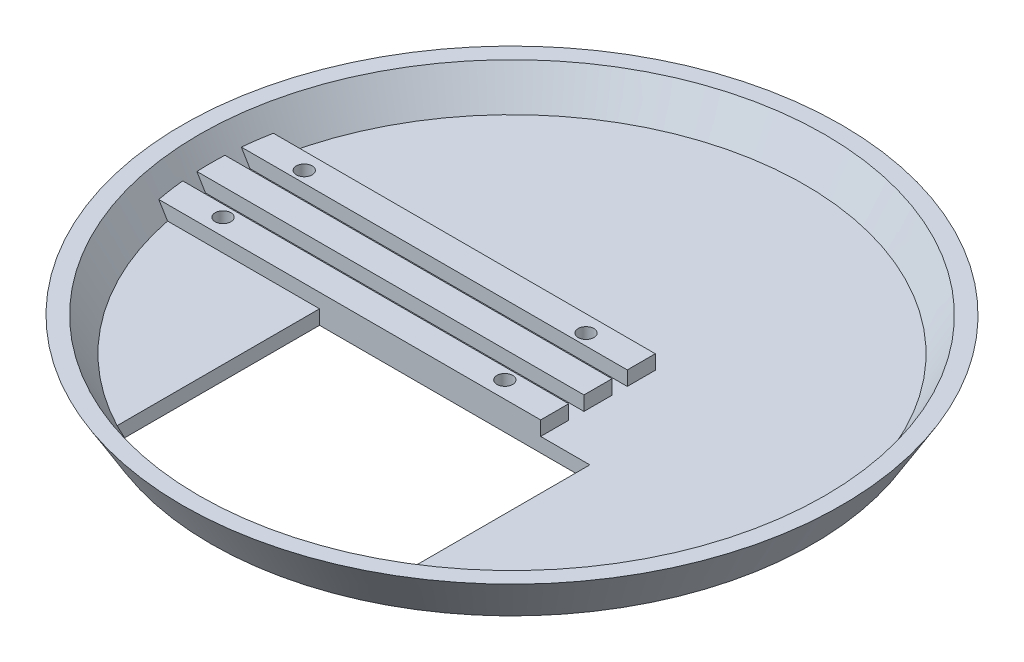
SolidWorks part; units mm, degrees
ref_plane "Front Plane" through (0, 0, 0) normal (0, 0, 1) x (1, 0, 0)
ref_plane "Top Plane" through (0, 0, 0) normal (0, 1, 0) x (1, 0, 0)
ref_plane "Right Plane" through (0, 0, 0) normal (1, 0, 0) x (0, 0, -1)
sketch "Sketch1" plane through (0, 0, 0) normal (0, 0, 1) x (1, 0, 0)
  line L0 (0, 0) -> (63, 0)
  line L1 (63, 0) -> (69, 10)
  line L6 (0, 3) -> (61.3014, 3)
  line L7 (61.3014, 3) -> (65.5014, 10)
  line L8 (69, 10) -> (65.5014, 10)
  line L9 (0, 0) -> (0, 3)
  line L10 (61.3014, 3) -> (66.4275, 11.5435) construction
  dimension "D1" = 69
  dimension "D2" = 63
  dimension "D3" = 10
  dimension "D4" = 3
revolve "Revolve1" add sketch "Sketch1" angle 360 about L9
sketch "Sketch2" plane through (0, 3, 0) normal (0, 1, 0) x (1, 0, 0)
  line L0 (-28.3, -12) -> (-28.3, -54.3781)
  line L1 (-28.3, -12) -> (28.3, -12)
  line L5 (28.3, -12) -> (28.3, -54.3781)
  arc A0 (-28.3, -54.3781) -> (28.3, -54.3781) centre (0, 0) ccw
  circle A3 centre (0, 0) radius 61.3014 construction
  dimension "D2" = 28.3
  dimension "D1" = 56.6
  dimension "D4" = 12
extrude "Cut-Extrude1" cut sketch "Sketch2" against normal through all
sketch "Sketch4" plane through (0, 0, 0) normal (1, 0, 0) x (0, 0, -1)
  line L0 (-6.1333, 3) -> (-12, 3)
  line L5 (-12, 3) -> (-12, 6)
  line L6 (-12, 6) -> (-6.1333, 6)
  line L7 (-6.1333, 6) -> (-6.1333, 3)
  line L8 (-2.9333, 3) -> (2.9333, 3)
  line L9 (2.9333, 3) -> (2.9333, 6)
  line L10 (2.9333, 6) -> (-2.9333, 6)
  line L11 (-2.9333, 6) -> (-2.9333, 3)
  line L12 (12, 3) -> (6.1333, 3)
  line L13 (6.1333, 3) -> (6.1333, 6)
  line L14 (6.1333, 6) -> (12, 6)
  line L15 (12, 6) -> (12, 3)
  point P13 (0, 3)
  dimension "D1" = 12
  dimension "D2" = 3
  dimension "D3" = 3
  dimension "D4" = 3.2
  dimension "D5" = 3.2
  dimension "D6" = 12
extrude "Boss-Extrude1" add sketch "Sketch4" along normal blind 10 and the other way blind 63.5
sketch "Sketch5" plane through (0, 0, 0) normal (0, 1, 0) x (1, 0, 0)
  line L0 (10, 2.9333) -> (10, -2.9333) construction
  circle A0 centre (7, -8.5) radius 1.65
  circle A1 centre (7, 0) radius 1.65
  circle A2 centre (7, 8.5) radius 1.65
  circle A6 centre (-52, 8.5) radius 1.65
  circle A8 centre (-52, -8.5) radius 1.65
  circle A9 centre (-22.5, 0) radius 1.65 [skipped]
  circle A10 centre (-52, 0) radius 1.65 [skipped]
  circle A11 centre (-22.5, 8.5) radius 1.65 [skipped]
  circle A12 centre (-22.5, -8.5) radius 1.65 [skipped]
  dimension "D2" = 3.3
  dimension "D3" = 8.5
  dimension "D6" = 3
  dimension "D7" = 59
  dimension "D4" = 8.5
  dimension "D5" = 3
extrude "Cut-Extrude2" cut sketch "Sketch5" along normal through all contours A2 | A0 | A8 | A6
sketch "Sketch7" [suppressed] plane through (10, 0, 0) normal (1, 0, 0) x (0, 0, -1)
  line L0 (-12, 37.9) -> (-6.1333, 37.9) construction
  line L1 (-12, 3) -> (-6.1333, 3)
  line L2 (-12, 3) -> (-12, 43)
  line L3 (-12, 43) -> (12, 43)
  line L4 (12, 3) -> (12, 43)
  line L5 (-2.9333, 37.9) -> (2.9333, 37.9) construction
  line L6 (-6.1333, 37.9) -> (-2.9333, 37.9)
  line L7 (-6.1333, 37.9) -> (-6.1333, 40.9)
  line L8 (-6.1333, 40.9) -> (-2.9333, 40.9)
  line L9 (-2.9333, 37.9) -> (-2.9333, 40.9)
  line L10 (12, 37.9) -> (6.1333, 37.9) construction
  line L11 (2.9333, 3) -> (2.9333, 6)
  line L12 (2.9333, 37.9) -> (6.1333, 37.9)
  line L13 (2.9333, 37.9) -> (2.9333, 40.9)
  line L14 (2.9333, 40.9) -> (6.1333, 40.9)
  line L15 (6.1333, 37.9) -> (6.1333, 40.9)
  line L20 (2.9333, 6) -> (6.1333, 6)
  line L21 (6.1333, 6) -> (6.1333, 3)
  line L22 (-6.1333, 3) -> (-6.1333, 6)
  line L23 (-6.1333, 6) -> (-2.9333, 6)
  line L24 (-2.9333, 6) -> (-2.9333, 3)
  line L25 (6.1333, 3) -> (12, 3)
  line L26 (-2.9333, 3) -> (2.9333, 3)
  circle A0 centre (0, 23.5) radius 8.5
  point P17 (0, 0)
  point P18 (0, 3)
  dimension "D6" = 17
  dimension "D7" = 20.5
  dimension "D1" = 24
  dimension "D2" = 40
  dimension "D3" = 3.2
  dimension "D4" = 3
  dimension "D5" = 37.9
sketch "Sketch8" plane through (10, 0, 0) normal (1, 0, 0) x (0, 0, -1)
  line L1 (-12, 6) -> (-6.1333, 6)
  line L2 (-12, 6) -> (-12, 3)
  line L3 (-12, 3) -> (-6.1333, 3)
  line L4 (-6.1333, 6) -> (-6.1333, 3)
  line L5 (-2.9333, 6) -> (2.9333, 6)
  line L6 (-2.9333, 6) -> (-2.9333, 3)
  line L7 (-2.9333, 3) -> (2.9333, 3)
  line L8 (2.9333, 6) -> (2.9333, 3)
  line L9 (6.1333, 6) -> (12, 6)
  line L10 (6.1333, 6) -> (6.1333, 3)
  line L11 (6.1333, 3) -> (12, 3)
  line L12 (12, 6) -> (12, 3)
extrude "Boss-Extrude3" add sketch "Sketch8" along normal blind 8
